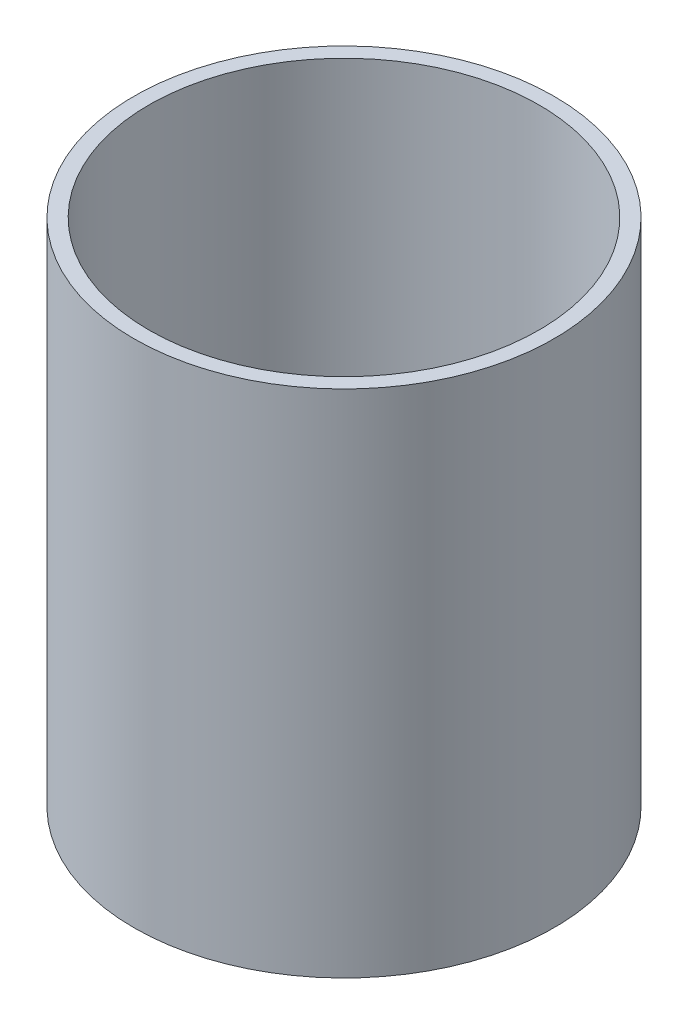
SolidWorks part; units mm, degrees
material "Corrugated Paper"
ref_plane "Front Plane" through (0, 0, 0) normal (0, 0, 1) x (1, 0, 0)
ref_plane "Top Plane" through (0, 0, 0) normal (0, 1, 0) x (1, 0, 0)
ref_plane "Right Plane" through (0, 0, 0) normal (1, 0, 0) x (0, 0, -1)
ref_axis "Axis1" through (0, 55, 0) along (0, -1, 0)
sketch "Sketch1" plane through (0, 0, 0) normal (0, 0, 1) x (1, 0, 0)
  line L1 (-44.45, 36.9791) -> (-41.275, 36.9791)
  line L2 (-44.45, 36.9791) -> (-44.45, -70.9709)
  line L3 (-44.45, -70.9709) -> (-41.275, -70.9709)
  line L4 (-41.275, 36.9791) -> (-41.275, -70.9709)
  line L5 (0, 36.9791) -> (-38.1, 36.9791) construction
  line L6 (0, -70.9709) -> (-38.1, -70.9709) construction
revolve "Revolve1" add sketch "Sketch1" angle 360 about axis through (0, 55, 0) along (0, -1, 0)
